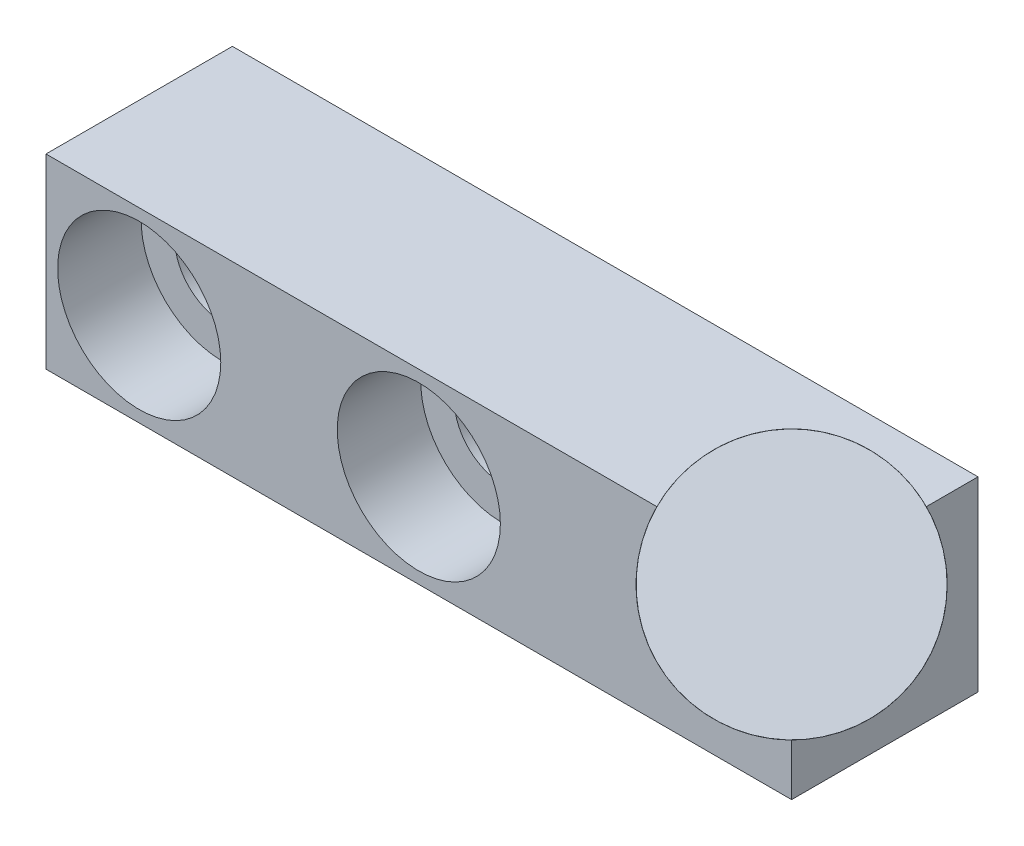
SolidWorks part; units mm, degrees
ref_plane "Front Plane" through (0, 0, 0) normal (0, 0, 1) x (1, 0, 0)
ref_plane "Top Plane" through (0, 0, 0) normal (0, 1, 0) x (1, 0, 0)
ref_plane "Right Plane" through (0, 0, 0) normal (1, 0, 0) x (0, 0, -1)
sketch "Sketch1" plane through (0, 0, 0) normal (0, 0, 1) x (1, 0, 0)
  line L1 (-12.7, -3.175) -> (12.7, -3.175)
  line L2 (-12.7, -3.175) -> (-12.7, 3.175)
  line L3 (-12.7, 3.175) -> (12.7, 3.175)
  line L4 (12.7, -3.175) -> (12.7, 3.175)
  line L5 (-12.7, -3.175) -> (12.7, 3.175) construction
  line L6 (-12.7, 3.175) -> (12.7, -3.175) construction
  point P0 (0, 0)
  dimension "D1" = 25.4
  dimension "D2" = 6.35
extrude "Boss-Extrude1" add sketch "Sketch1" along normal blind 6.35 contours L3 L4 L1 L2
hole_wizard "CBORE for #4 Socket Head Cap Screw1" positions "Sketch2" profile "Sketch3" counterbore size "#4" standard "ANSI Inch"
sketch "Sketch2" plane through (0, 0, 6.35) normal (0, 0, 1) x (1, 0, 0)
  line L0 (-12.7, -3.175) -> (-12.7, 3.175) construction
  line L1 (-12.7, -3.175) -> (12.7, -3.175) construction
  point P0 (-9.525, 0)
  point P2 (0, 0)
  dimension "D1" = 3.175
  dimension "D2" = 3.175
  dimension "D3" = 3.175
  dimension "D4" = 9.525
sketch "Sketch3" plane through (-9.525, 0, 6.35) normal (1, 0, 0) x (0, -1, 0)
  line L0 (0, 0) -> (0, 8.5752)
  line L1 (0, 8.5752) -> (1.6319, 7.5946)
  line L2 (1.6319, 7.5946) -> (1.6319, 2.8448)
  line L3 (1.6319, 2.8448) -> (2.7788, 2.8448)
  line L4 (2.7788, 2.8448) -> (2.7788, 0)
  line L5 (2.7788, 0) -> (0, 0)
  line L10 (0, 8.5752) -> (-1.632, 7.5946) construction
  line L11 (0, -6.35) -> (0, 107.95) construction
  dimension "Hole Dia." = 3.2639
  dimension "Hole Depth" = 7.5946
  dimension "C'Bore Dia." = 5.5575
  dimension "C'Bore Depth" = 2.8448
  dimension "Drill Angle" = 118
ref_point "Point1" parameters "D1"=6.35
ref_axis "Axis3" through (6.35, -3.175, 0) along (0.5774, 0.5774, 0.5774)
ref_plane "Plane1" through (12.7, 3.175, 6.35) normal (0.5774, 0.5774, 0.5774) x (0.4082, 0.4082, -0.8165)
sketch "Sketch4" plane through (12.7, 3.175, 6.35) normal (0.5774, 0.5774, 0.5774) x (0.4082, 0.4082, -0.8165)
  circle A1 centre (0, 0) radius 3.7465
  dimension "D1" = 7.493
extrude "Boss-Extrude2" add sketch "Sketch4" against normal blind 5.715 contours A1
